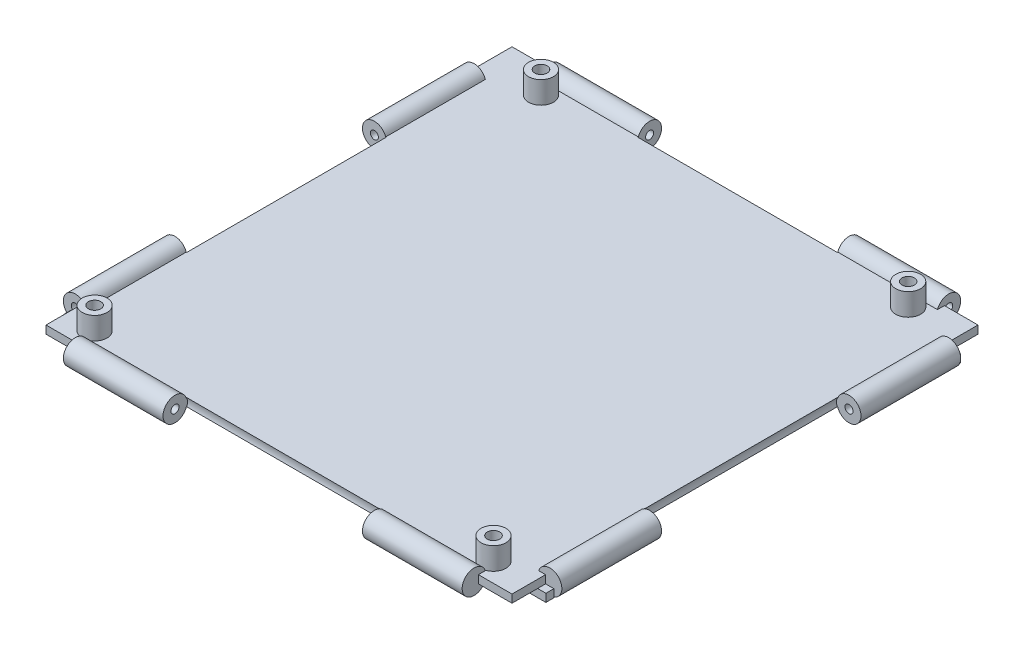
SolidWorks part; units mm, degrees
ref_plane "Front Plane" through (0, 0, 0) normal (0, 0, 1) x (1, 0, 0)
ref_plane "Top Plane" through (0, 0, 0) normal (0, 1, 0) x (1, 0, 0)
ref_plane "Right Plane" through (0, 0, 0) normal (1, 0, 0) x (0, 0, -1)
sketch "Sketch3" plane through (0, 0, 0) normal (0, 1, 0) x (1, 0, 0)
  line L1 (-48.5, -48.5) -> (48.5, -48.5)
  line L2 (-48.5, -48.5) -> (-48.5, 48.5)
  line L3 (-48.5, 48.5) -> (48.5, 48.5)
  line L4 (48.5, -48.5) -> (48.5, 48.5)
  line L5 (-48.5, -48.5) -> (48.5, 48.5) construction
  line L6 (-48.5, 48.5) -> (48.5, -48.5) construction
  point P0 (0, 0)
extrude "Boss-Extrude2" add sketch "Sketch3" along normal blind 1.6
sketch "Sketch6" plane through (0, 0, 48.5) normal (0, 0, 1) x (1, 0, 0)
  line L0 (-48.5, 1.6) -> (-48.5, 0) construction
  circle A0 centre (-47.6, 0.8) radius 2.4
  point P2 (-48.5, 0.8)
  point P5 (-48.5, 0.8)
  dimension "D1" = 0.9
  dimension "D2" = 0
extrude "Boss-Extrude3" add sketch "Sketch6" against normal blind 25
sketch "Sketch8" plane through (0, 0, 48.5) normal (0, 0, 1) x (1, 0, 0)
  line L0 (48.5, 1.6) -> (48.5, 0) construction
  line L1 (-45.3373, 0) -> (48.5, 0) construction
  circle A0 centre (47.6, 0.8) radius 2.4
  point P2 (48.5, 0.8)
  dimension "D1" = 0.9
  dimension "D2" = 0.8
extrude "Boss-Extrude4" add sketch "Sketch8" against normal blind 25
sketch "Sketch10" plane through (0, 0, -48.5) normal (0, 0, -1) x (-1, 0, 0)
  circle A0 centre (-47.6, 0.8) radius 2.4
extrude "Boss-Extrude5" add sketch "Sketch10" against normal blind 25
sketch "Sketch11" plane through (0, 0, -48.5) normal (0, 0, -1) x (-1, 0, 0)
  circle A0 centre (47.6, 0.8) radius 2.4
extrude "Boss-Extrude6" add sketch "Sketch11" against normal blind 25
sketch "Sketch12" plane through (-48.5, 0, 0) normal (-1, 0, 0) x (0, 0, 1)
  line L0 (-23.5, 3.2) -> (-48.5, 3.2) construction
  line L1 (-48.5, 3.2) -> (-48.5, -1.6) construction
  circle A0 centre (-47.6, 0.8) radius 2.4
  point P4 (-48.5, 0.8)
  dimension "D1" = 2.4
  dimension "D2" = 0.9
extrude "Boss-Extrude7" add sketch "Sketch12" against normal blind 25
sketch "Sketch13" plane through (-48.5, 0, 0) normal (-1, 0, 0) x (0, 0, 1)
  line L0 (48.5, 3.2) -> (23.5, 3.2) construction
  line L1 (48.5, -1.6) -> (48.5, 3.2) construction
  circle A0 centre (47.6, 0.8) radius 2.4
  dimension "D1" = 2.4
  dimension "D2" = 0.9
extrude "Boss-Extrude8" add sketch "Sketch13" against normal blind 25
sketch "Sketch15" plane through (48.5, 0, 0) normal (1, 0, 0) x (0, 0, -1)
  circle A0 centre (-47.6, 0.8) radius 2.4
extrude "Boss-Extrude9" add sketch "Sketch15" against normal blind 25
sketch "Sketch16" plane through (48.5, 0, 0) normal (1, 0, 0) x (0, 0, -1)
  circle A0 centre (47.6, 0.8) radius 2.4
extrude "Boss-Extrude10" add sketch "Sketch16" against normal blind 25
sketch "Sketch24" plane through (0, 0, 48.5) normal (0, 0, 1) x (1, 0, 0)
  line L1 (-45.2, -1.9741) -> (-50, -1.9741)
  line L2 (-45.2, -1.9741) -> (-45.2, 3.5741)
  line L3 (-45.2, 3.5741) -> (-50, 3.5741)
  line L4 (-50, -1.9741) -> (-50, 3.5741)
  line L5 (-45.2, -1.9741) -> (-50, 3.5741) construction
  line L6 (-45.2, 3.5741) -> (-50, -1.9741) construction
  point P0 (-47.6, 0.8)
extrude "Cut-Extrude6" cut sketch "Sketch24" against normal blind 3.3
sketch "Sketch25" plane through (0, 0, 48.5) normal (0, 0, -1) x (-1, 0, 0)
  line L1 (50, -1.6) -> (45.2, -1.6)
  line L2 (50, -1.6) -> (50, 3.2)
  line L3 (50, 3.2) -> (45.2, 3.2)
  line L4 (45.2, -1.6) -> (45.2, 3.2)
  line L5 (50, -1.6) -> (45.2, 3.2) construction
  line L6 (50, 3.2) -> (45.2, -1.6) construction
  point P0 (47.6, 0.8)
extrude "Cut-Extrude7" cut sketch "Sketch25" against normal blind 3.3
sketch "Sketch27" plane through (0, 0, -48.5) normal (0, 0, -1) x (-1, 0, 0)
  line L1 (45.2, -1.7788) -> (50, -1.7788)
  line L2 (45.2, -1.7788) -> (45.2, 3.3788)
  line L3 (45.2, 3.3788) -> (50, 3.3788)
  line L4 (50, -1.7788) -> (50, 3.3788)
  line L5 (45.2, -1.7788) -> (50, 3.3788) construction
  line L6 (45.2, 3.3788) -> (50, -1.7788) construction
  point P0 (47.6, 0.8)
extrude "Cut-Extrude8" cut sketch "Sketch27" against normal blind 3.3
sketch "Sketch28" plane through (0, 0, -45.2) normal (0, 0, -1) x (-1, 0, 0)
  line L1 (50, -1.6) -> (45.2, -1.6)
  line L2 (50, -1.6) -> (50, 3.2)
  line L3 (50, 3.2) -> (45.2, 3.2)
  line L4 (45.2, -1.6) -> (45.2, 3.2)
  line L5 (50, -1.6) -> (45.2, 3.2) construction
  line L6 (50, 3.2) -> (45.2, -1.6) construction
  point P0 (47.6, 0.8)
extrude "Cut-Extrude9" cut sketch "Sketch28" along normal blind 6
sketch "Sketch29" plane through (0, 0, 48.5) normal (0, 0, 1) x (1, 0, 0)
  line L1 (45.2, -1.9133) -> (50, -1.9133)
  line L2 (45.2, -1.9133) -> (45.2, 3.5133)
  line L3 (45.2, 3.5133) -> (50, 3.5133)
  line L4 (50, -1.9133) -> (50, 3.5133)
  line L5 (45.2, -1.9133) -> (50, 3.5133) construction
  line L6 (45.2, 3.5133) -> (50, -1.9133) construction
  point P0 (47.6, 0.8)
extrude "Cut-Extrude10" cut sketch "Sketch29" against normal blind 3.3
sketch "Sketch30" plane through (0, 0, 48.5) normal (0, 0, -1) x (-1, 0, 0)
  line L1 (-45.2, 3.2) -> (-50.2988, 3.2)
  line L2 (-45.2, 3.2) -> (-45.2, -1.6)
  line L3 (-45.2, -1.6) -> (-50.2988, -1.6)
  line L4 (-50.2988, 3.2) -> (-50.2988, -1.6)
extrude "Cut-Extrude11" cut sketch "Sketch30" against normal blind 3.3
sketch "Sketch31" plane through (0, 0, -48.5) normal (0, 0, -1) x (-1, 0, 0)
  line L1 (-45.2, -1.9404) -> (-50, -1.9404)
  line L2 (-45.2, -1.9404) -> (-45.2, 3.5404)
  line L3 (-45.2, 3.5404) -> (-50, 3.5404)
  line L4 (-50, -1.9404) -> (-50, 3.5404)
  line L5 (-45.2, -1.9404) -> (-50, 3.5404) construction
  line L6 (-45.2, 3.5404) -> (-50, -1.9404) construction
  point P0 (-47.6, 0.8)
extrude "Cut-Extrude12" cut sketch "Sketch31" against normal blind 3.3
sketch "Sketch32" plane through (0, 0, -48.5) normal (0, 0, 1) x (1, 0, 0)
  line L1 (45.2, 3.2) -> (50.1875, 3.2)
  line L2 (45.2, 3.2) -> (45.2, -1.6)
  line L3 (45.2, -1.6) -> (50.1875, -1.6)
  line L4 (50.1875, 3.2) -> (50.1875, -1.6)
extrude "Cut-Extrude13" cut sketch "Sketch32" against normal blind 3.3
sketch "Sketch38" plane through (0, 0, -23.5) normal (0, 0, 1) x (1, 0, 0)
  circle A0 centre (-47.6, 0.8) radius 2.4
extrude "Boss-Extrude11" add sketch "Sketch38" along normal blind 1
sketch "Sketch39" plane through (0, 0, 23.5) normal (0, 0, -1) x (-1, 0, 0)
  circle A0 centre (47.6, 0.8) radius 2.4
extrude "Boss-Extrude12" add sketch "Sketch39" along normal blind 1
sketch "Sketch42" plane through (0, 0, -23.5) normal (0, 0, 1) x (1, 0, 0)
  circle A0 centre (47.6, 0.8) radius 2.4
extrude "Boss-Extrude13" add sketch "Sketch42" along normal blind 1
sketch "Sketch43" plane through (0, 0, 23.5) normal (0, 0, -1) x (-1, 0, 0)
  circle A0 centre (-47.6, 0.8) radius 2.4
extrude "Boss-Extrude14" add sketch "Sketch43" along normal blind 1
sketch "Sketch44" plane through (23.5, 0, 0) normal (-1, 0, 0) x (0, 0, 1)
  circle A0 centre (-47.6, 0.8) radius 2.4
extrude "Boss-Extrude15" add sketch "Sketch44" along normal blind 1
sketch "Sketch45" plane through (-23.5, 0, 0) normal (1, 0, 0) x (0, 0, -1)
  circle A0 centre (47.6, 0.8) radius 2.4
extrude "Boss-Extrude16" add sketch "Sketch45" along normal blind 1
sketch "Sketch46" plane through (23.5, 0, 0) normal (-1, 0, 0) x (0, 0, 1)
  circle A0 centre (47.6, 0.8) radius 2.4
extrude "Boss-Extrude17" add sketch "Sketch46" along normal blind 1
sketch "Sketch47" plane through (-23.5, 0, 0) normal (1, 0, 0) x (0, 0, -1)
  circle A0 centre (-47.6, 0.8) radius 2.4
extrude "Boss-Extrude18" add sketch "Sketch47" along normal blind 1
sketch "Sketch69" plane through (0, 0, 45.2) normal (0, 0, 1) x (1, 0, 0)
  line L0 (-45.3373, 1.6) -> (-46.7373, 1.6)
  line L1 (-46.7373, 1.6) -> (-46.7373, 0)
  line L2 (-46.7373, 0) -> (-45.3373, 0)
  line L3 (-45.3373, 0) -> (-45.3373, -2.2963)
  line L4 (-45.3373, -2.2963) -> (-50.8618, -2.2963)
  line L5 (-50.8618, -2.2963) -> (-50.8618, 4.0891)
  line L6 (-50.8618, 4.0891) -> (-45.3373, 4.0891)
  line L7 (-45.3373, 4.0891) -> (-45.3373, 1.6)
extrude "Cut-Extrude24" cut sketch "Sketch69" against normal blind 5.2
sketch "Sketch72" plane through (0, 0, 45.2) normal (0, 0, 1) x (1, 0, 0)
  line L0 (45.3373, 1.6) -> (46.7373, 1.6)
  line L1 (46.7373, 1.6) -> (46.7373, 0)
  line L2 (46.7373, 0) -> (45.3373, 0)
  line L3 (45.3373, 0) -> (45.3373, -2.332)
  line L4 (45.3373, -2.332) -> (51.5664, -2.332)
  line L5 (51.5664, -2.332) -> (51.5664, 3.8868)
  line L6 (51.5664, 3.8868) -> (45.3373, 3.8868)
  line L7 (45.3373, 3.8868) -> (45.3373, 1.6)
extrude "Cut-Extrude25" cut sketch "Sketch72" against normal blind 5.2
sketch "Sketch74" plane through (0, 0, -45.2) normal (0, 0, -1) x (-1, 0, 0)
  line L0 (-45.3373, 1.6) -> (-46.7373, 1.6)
  line L1 (-46.7373, 1.6) -> (-46.7373, 0)
  line L2 (-46.7373, 0) -> (-45.3373, 0)
  line L3 (-45.3373, 0) -> (-45.3373, -2.1525)
  line L4 (-45.3373, -2.1525) -> (-50.4022, -2.1525)
  line L5 (-50.4022, -2.1525) -> (-50.4022, 3.9519)
  line L6 (-50.4022, 3.9519) -> (-45.3373, 3.9519)
  line L7 (-45.3373, 3.9519) -> (-45.3373, 1.6)
extrude "Cut-Extrude26" cut sketch "Sketch74" against normal blind 5.2
sketch "Sketch75" plane through (0, 0, -45.2) normal (0, 0, -1) x (-1, 0, 0)
  line L0 (45.3373, 1.6) -> (46.7373, 1.6)
  line L1 (46.7373, 1.6) -> (46.7373, 0)
  line L2 (46.7373, 0) -> (45.3373, 0)
  line L3 (45.3373, 0) -> (45.3373, -1.8864)
  line L4 (45.3373, -1.8864) -> (51.292, -1.8864)
  line L5 (51.292, -1.8864) -> (51.292, 3.8238)
  line L6 (51.292, 3.8238) -> (45.3373, 3.8238)
  line L7 (45.3373, 3.8238) -> (45.3373, 1.6)
extrude "Cut-Extrude27" cut sketch "Sketch75" against normal blind 5.2
sketch "Sketch77" plane through (-45.2, 0, 0) normal (-1, 0, 0) x (0, 0, 1)
  line L0 (-45.3373, 1.6) -> (-45.3373, 4.0728)
  line L1 (-45.3373, 4.0728) -> (-50.7539, 4.0728)
  line L2 (-50.7539, 4.0728) -> (-50.7539, -2.0737)
  line L3 (-50.7539, -2.0737) -> (-45.3373, -2.0737)
  line L4 (-45.3373, -2.0737) -> (-45.3373, 0)
  line L5 (-45.3373, 0) -> (-46.7373, 0)
  line L6 (-46.7373, 0) -> (-46.7373, 1.6)
  line L7 (-46.7373, 1.6) -> (-45.3373, 1.6)
extrude "Cut-Extrude29" cut sketch "Sketch77" against normal blind 5.2
sketch "Sketch78" plane through (-45.2, 0, 0) normal (-1, 0, 0) x (0, 0, 1)
  line L0 (45.3373, 1.6) -> (45.3373, 3.5518)
  line L1 (45.3373, 3.5518) -> (50.6981, 3.5518)
  line L2 (50.6981, 3.5518) -> (50.6981, -1.7977)
  line L3 (50.6981, -1.7977) -> (45.3373, -1.7977)
  line L4 (45.3373, -1.7977) -> (45.3373, 0)
  line L5 (45.3373, 0) -> (46.7373, 0)
  line L6 (46.7373, 0) -> (46.7373, 1.6)
  line L7 (46.7373, 1.6) -> (45.3373, 1.6)
extrude "Cut-Extrude30" cut sketch "Sketch78" against normal blind 5.2
sketch "Sketch79" plane through (45.2, 0, 0) normal (1, 0, 0) x (0, 0, -1)
  line L0 (-45.3373, 1.6) -> (-45.3373, 4.0003)
  line L1 (-45.3373, 4.0003) -> (-50.7843, 4.0003)
  line L2 (-50.7843, 4.0003) -> (-50.7843, -1.8519)
  line L3 (-50.7843, -1.8519) -> (-45.3373, -1.8519)
  line L4 (-45.3373, -1.8519) -> (-45.3373, 0)
  line L5 (-45.3373, 0) -> (-46.7373, 0)
  line L6 (-46.7373, 0) -> (-46.7373, 1.6)
  line L7 (-46.7373, 1.6) -> (-45.3373, 1.6)
extrude "Cut-Extrude31" cut sketch "Sketch79" against normal blind 5.2
sketch "Sketch80" plane through (45.2, 0, 0) normal (1, 0, 0) x (0, 0, -1)
  line L0 (45.3373, 1.6) -> (45.3373, 3.7938)
  line L1 (45.3373, 3.7938) -> (50.5196, 3.7938)
  line L2 (50.5196, 3.7938) -> (50.5196, -2.0451)
  line L3 (50.5196, -2.0451) -> (45.3373, -2.0451)
  line L4 (45.3373, -2.0451) -> (45.3373, 0)
  line L5 (45.3373, 0) -> (46.7373, 0)
  line L6 (46.7373, 0) -> (46.7373, 1.6)
  line L7 (46.7373, 1.6) -> (45.3373, 1.6)
extrude "Cut-Extrude32" cut sketch "Sketch80" against normal blind 5.2
sketch "Sketch81" plane through (0, 1.6, 0) normal (0, 1, 0) x (1, 0, 0)
  line L1 (-45.2, 46.7373) -> (-46.7373, 46.7373)
  line L2 (-45.2, 46.7373) -> (-45.2, 45.2)
  line L3 (-45.2, 45.2) -> (-46.7373, 45.2)
  line L4 (-46.7373, 46.7373) -> (-46.7373, 45.2)
extrude "Boss-Extrude21" add sketch "Sketch81" against normal blind 1.6
sketch "Sketch82" plane through (0, 1.6, 0) normal (0, 1, 0) x (1, 0, 0)
  line L1 (45.2, 46.7373) -> (46.7373, 46.7373)
  line L2 (45.2, 46.7373) -> (45.2, 45.2)
  line L3 (45.2, 45.2) -> (46.7373, 45.2)
  line L4 (46.7373, 46.7373) -> (46.7373, 45.2)
extrude "Boss-Extrude22" add sketch "Sketch82" against normal blind 1.6
sketch "Sketch83" plane through (0, 1.6, 0) normal (0, 1, 0) x (1, 0, 0)
  line L1 (-46.7373, -45.2) -> (-45.2, -45.2)
  line L2 (-46.7373, -45.2) -> (-46.7373, -46.7373)
  line L3 (-46.7373, -46.7373) -> (-45.2, -46.7373)
  line L4 (-45.2, -45.2) -> (-45.2, -46.7373)
extrude "Boss-Extrude23" add sketch "Sketch83" against normal blind 1.6
sketch "Sketch84" plane through (0, 1.6, 0) normal (0, 1, 0) x (1, 0, 0)
  line L1 (46.7373, -45.2) -> (45.2, -45.2)
  line L2 (46.7373, -45.2) -> (46.7373, -46.7373)
  line L3 (46.7373, -46.7373) -> (45.2, -46.7373)
  line L4 (45.2, -45.2) -> (45.2, -46.7373)
extrude "Boss-Extrude24" add sketch "Sketch84" against normal blind 1.6
sketch "Sketch87" plane through (-22.5, 0, 0) normal (1, 0, 0) x (0, 0, -1)
  circle A0 centre (-47.6, 0.8) radius 2.4
extrude "Boss-Extrude25" add sketch "Sketch87" along normal blind 2.5
sketch "Sketch88" plane through (22.5, 0, 0) normal (-1, 0, 0) x (0, 0, 1)
  circle A0 centre (47.6, 0.8) radius 2.4
extrude "Boss-Extrude26" add sketch "Sketch88" along normal blind 2.5
sketch "Sketch91" plane through (-20, 0, 0) normal (1, 0, 0) x (0, 0, -1)
  circle A0 centre (-47.6, 0.8) radius 2.5
extrude "Cut-Extrude33" cut sketch "Sketch91" along normal blind 40
sketch "Sketch93" plane through (0, 0, -22.5) normal (0, 0, 1) x (1, 0, 0)
  circle A0 centre (-47.6, 0.8) radius 2.4
extrude "Boss-Extrude27" add sketch "Sketch93" along normal blind 2.5
sketch "Sketch94" plane through (0, 0, 22.5) normal (0, 0, -1) x (-1, 0, 0)
  circle A0 centre (47.6, 0.8) radius 2.4
extrude "Boss-Extrude28" add sketch "Sketch94" along normal blind 2.5
sketch "Sketch97" plane through (0, 0, -20) normal (0, 0, 1) x (1, 0, 0)
  circle A0 centre (-47.6, 0.8) radius 2.5
extrude "Cut-Extrude34" cut sketch "Sketch97" along normal blind 40
sketch "Sketch98" plane through (0, 0, -22.5) normal (0, 0, 1) x (1, 0, 0)
  circle A0 centre (47.6, 0.8) radius 2.4
extrude "Boss-Extrude29" add sketch "Sketch98" along normal blind 2.5
sketch "Sketch99" plane through (0, 0, 22.5) normal (0, 0, -1) x (-1, 0, 0)
  circle A0 centre (-47.6, 0.8) radius 2.4
extrude "Boss-Extrude30" add sketch "Sketch99" along normal blind 2.5
sketch "Sketch100" plane through (0, 0, -20) normal (0, 0, 1) x (1, 0, 0)
  circle A0 centre (47.6, 0.8) radius 2.5
extrude "Cut-Extrude35" cut sketch "Sketch100" along normal blind 40
sketch "Sketch101" plane through (-22.5, 0, 0) normal (1, 0, 0) x (0, 0, -1)
  circle A0 centre (47.6, 0.8) radius 2.4
extrude "Boss-Extrude31" add sketch "Sketch101" along normal blind 2.5
sketch "Sketch102" plane through (22.5, 0, 0) normal (-1, 0, 0) x (0, 0, 1)
  circle A0 centre (-47.6, 0.8) radius 2.4
extrude "Boss-Extrude32" add sketch "Sketch102" along normal blind 2.5
sketch "Sketch104" plane through (-20, 0, 0) normal (1, 0, 0) x (0, 0, -1)
  circle A0 centre (47.6, 0.8) radius 2.5
extrude "Cut-Extrude36" cut sketch "Sketch104" along normal blind 40
sketch "Sketch105" plane through (0, 0, 40) normal (0, 0, 1) x (1, 0, 0)
  circle A0 centre (-47.6, 0.8) radius 0.81
extrude "Cut-Extrude37" cut sketch "Sketch105" against normal blind 78.5
sketch "Sketch106" plane through (-40, 0, 0) normal (-1, 0, 0) x (0, 0, 1)
  circle A0 centre (47.6, 0.8) radius 0.81
extrude "Cut-Extrude38" cut sketch "Sketch106" against normal blind 78.5
sketch "Sketch107" plane through (40, 0, 0) normal (1, 0, 0) x (0, 0, -1)
  circle A0 centre (47.6, 0.8) radius 0.81
extrude "Cut-Extrude39" cut sketch "Sketch107" against normal blind 78.5
sketch "Sketch108" plane through (0, 0, -40) normal (0, 0, -1) x (-1, 0, 0)
  circle A0 centre (-47.6, 0.8) radius 0.81
extrude "Cut-Extrude40" cut sketch "Sketch108" against normal blind 78.5
sketch "Sketch135" plane through (0, 1.6, 0) normal (0, 1, 0) x (1, 0, 0)
  line L2 (28.1604, 35.2315) -> (0, 7.0711)
  line L3 (0, 7.0711) -> (-28.1604, 35.2315)
  line L4 (-28.1604, 35.2315) -> (28.1604, 35.2315)
  line L5 (-20, 45.2315) -> (20, 45.2315) construction
  dimension "D1" = 10
extrude "Cut-Extrude47" cut sketch "Sketch135" against normal blind 20
sketch "Sketch136" plane through (0, 1.6, 0) normal (0, 1, 0) x (1, 0, 0)
  line L2 (-28.1604, -35.2315) -> (0, -7.0711)
  line L3 (0, -7.0711) -> (28.1604, -35.2315)
  line L4 (28.1604, -35.2315) -> (-28.1604, -35.2315)
  line L5 (20, -45.2315) -> (-20, -45.2315) construction
  dimension "D3" = 10
extrude "Cut-Extrude48" cut sketch "Sketch136" against normal blind 20
sketch "Sketch137" plane through (0, 1.6, 0) normal (0, 1, 0) x (1, 0, 0)
  line L0 (35.2315, 28.1604) -> (7.0711, 0)
  line L1 (7.0711, 0) -> (35.2315, -28.1604)
  line L2 (35.2315, -28.1604) -> (35.2315, 28.1604)
  line L3 (0, 7.0711) -> (28.1604, 35.2315) construction
  line L4 (28.1604, -35.2315) -> (0, -7.0711) construction
  line L5 (45.2315, 20) -> (45.2315, -20) construction
  dimension "D1" = 10
  dimension "D2" = 10
  dimension "D3" = 10
extrude "Cut-Extrude49" cut sketch "Sketch137" against normal blind 20
sketch "Sketch138" plane through (0, 1.6, 0) normal (0, 1, 0) x (1, 0, 0)
  line L0 (-35.2315, 28.1604) -> (-7.0711, 0)
  line L1 (-7.0711, 0) -> (-35.2315, -28.1604)
  line L2 (-35.2315, -28.1604) -> (-35.2315, 28.1604)
  line L3 (-45.2315, -20) -> (-45.2315, 20) construction
  line L4 (0, -7.0711) -> (-28.1604, -35.2315) construction
  line L5 (-28.1604, 35.2315) -> (0, 7.0711) construction
  dimension "D1" = 10
  dimension "D2" = 10
  dimension "D3" = 10
extrude "Cut-Extrude50" cut sketch "Sketch138" against normal blind 20
sketch "Sketch139" plane through (0, 1.6, 0) normal (0, 1, 0) x (1, 0, 0)
  circle A0 centre (0, 0) radius 15
extrude "Boss-Extrude40" add sketch "Sketch139" against normal blind 1.6
sketch "Sketch140" plane through (0, 1.6, 0) normal (0, 1, 0) x (1, 0, 0)
  circle A0 centre (0, 0) radius 5
extrude "Cut-Extrude51" cut sketch "Sketch140" against normal blind 1.6
fillet "Fillet7" radius 2 16 edges at (28.1604, 0.8, -35.2315) (35.2315, 0.8, -28.1604) (35.2315, 0.8, 28.1604) (28.1604, 0.8, 35.2315) (-28.1604, 0.8, 35.2315) (-13.5355, 0.8, -6.4645) (-13.5355, 0.8, 6.4645) (-35.2315, 0.8, 28.1604) (6.4645, 0.8, -13.5355) (-6.4645, 0.8, -13.5355) (13.5355, 0.8, 6.4645) (13.5355, 0.8, -6.4645) (-6.4645, 0.8, 13.5355) (6.4645, 0.8, 13.5355) (-35.2315, 0.8, -28.1604) (-28.1604, 0.8, -35.2315)
sketch "Sketch119" plane through (0, 1.6, 0) normal (0, 1, 0) x (1, 0, 0)
  line L2 (-28.1604, 35.2315) -> (28.1604, 35.2315)
  line L3 (28.1604, 35.2315) -> (0, 7.0711)
  line L4 (0, 7.0711) -> (-28.1604, 35.2315)
  line L5 (-20, 45.2315) -> (20, 45.2315) construction
  dimension "D1" = 10
extrude "Cut-Extrude41" cut sketch "Sketch119" against normal blind 1.6
sketch "Sketch120" plane through (0, 1.6, 0) normal (0, 1, 0) x (1, 0, 0)
  line L2 (-28.1604, -35.2315) -> (28.1604, -35.2315)
  line L3 (28.1604, -35.2315) -> (0, -7.0711)
  line L4 (-28.1604, -35.2315) -> (0, -7.0711)
  line L5 (20, -45.2315) -> (-20, -45.2315) construction
  dimension "D3" = 10
extrude "Cut-Extrude42" cut sketch "Sketch120" against normal blind 1.6
sketch "Sketch121" plane through (0, 1.6, 0) normal (0, 1, 0) x (1, 0, 0)
  line L0 (-35.2315, 28.1604) -> (-35.2315, -28.1604)
  line L1 (-35.2315, -28.1604) -> (-7.0711, 0)
  line L2 (-35.2315, 28.1604) -> (-7.0711, 0)
  line L3 (-28.1604, 35.2315) -> (0, 7.0711) construction
  line L4 (0, -7.0711) -> (-28.1604, -35.2315) construction
  line L5 (-45.2315, -20) -> (-45.2315, 20) construction
  dimension "D1" = 10
  dimension "D2" = 10
  dimension "D3" = 10
extrude "Cut-Extrude43" cut sketch "Sketch121" against normal blind 1.6
sketch "Sketch122" plane through (0, 1.6, 0) normal (0, 1, 0) x (1, 0, 0)
  line L0 (35.2315, 28.1604) -> (35.2315, -28.1604)
  line L1 (35.2315, -28.1604) -> (7.0711, 0)
  line L2 (35.2315, 28.1604) -> (7.0711, 0)
  line L3 (0, 7.0711) -> (28.1604, 35.2315) construction
  line L4 (28.1604, -35.2315) -> (0, -7.0711) construction
  line L5 (45.2315, 20) -> (45.2315, -20) construction
  dimension "D1" = 10
  dimension "D2" = 10
  dimension "D3" = 10
extrude "Cut-Extrude44" cut sketch "Sketch122" against normal blind 1.6
sketch "Sketch123" plane through (0, 1.6, 0) normal (0, 1, 0) x (1, 0, 0)
  circle A0 centre (0, 0) radius 15
extrude "Boss-Extrude35" add sketch "Sketch123" against normal blind 1.6
sketch "Sketch124" plane through (0, 1.6, 0) normal (0, 1, 0) x (1, 0, 0)
  circle A0 centre (0, 0) radius 5
extrude "Cut-Extrude45" cut sketch "Sketch124" against normal blind 1.6
fillet "Fillet4" radius 2 16 edges at (35.2315, 0.8, 28.1604) (35.2315, 0.8, -28.1604) (-6.4645, 0.8, 13.5355) (6.4645, 0.8, 13.5355) (28.1604, 0.8, 35.2315) (13.5355, 0.8, -6.4645) (13.5355, 0.8, 6.4645) (-28.1604, 0.8, 35.2315) (-13.5355, 0.8, 6.4645) (-13.5355, 0.8, -6.4645) (28.1604, 0.8, -35.2315) (-28.1604, 0.8, -35.2315) (6.4645, 0.8, -13.5355) (-6.4645, 0.8, -13.5355) (-35.2315, 0.8, 28.1604) (-35.2315, 0.8, -28.1604)
sketch "Sketch144" plane through (0, 0, -46.7373) normal (0, 0, -1) x (-1, 0, 0)
  line L1 (46.7373, 1.6) -> (40, 1.6)
  line L2 (46.7373, 1.6) -> (46.7373, 0)
  line L3 (46.7373, 0) -> (40, 0)
  line L4 (40, 1.6) -> (40, 0)
extrude "Boss-Extrude42" add sketch "Sketch144" along normal blind 1.6
sketch "Sketch145" plane through (-46.7373, 0, 0) normal (-1, 0, 0) x (0, 0, 1)
  line L1 (-48.3373, 1.6) -> (-40, 1.6)
  line L2 (-48.3373, 1.6) -> (-48.3373, 0)
  line L3 (-48.3373, 0) -> (-40, 0)
  line L4 (-40, 1.6) -> (-40, 0)
extrude "Boss-Extrude43" add sketch "Sketch145" along normal blind 1.6
sketch "Sketch147" plane through (0, 0, 0) normal (0, -1, 0) x (1, 0, 0)
  line L0 (-40, -40) -> (-48.4, -40)
  line L1 (-50, -40) -> (-45.3373, -40) construction
  line L2 (-48.4, -40) -> (-48.4, -41.6)
  line L3 (-48.4, -41.6) -> (-40, -41.6)
  line L4 (-40, -41.6) -> (-40, -40)
  line L5 (-40, -45.3373) -> (-40, -48.3373) construction
  dimension "D1" = 1.6
  dimension "D2" = 8.4
  dimension "D3" = 0
extrude "Boss-Extrude44" add sketch "Sketch147" along normal blind 1.6
sketch "Sketch149" plane through (0, 0, 0) normal (0, -1, 0) x (1, 0, 0)
  line L0 (-45.3373, 40) -> (-50, 40) construction
  line L1 (-48.4, 40) -> (-40, 40)
  line L3 (-48.4, 40) -> (-48.4, 41.6)
  line L4 (-48.4, 41.6) -> (-40, 41.6)
  line L6 (-40, 40) -> (-40, 41.6)
  line L7 (-40, 50) -> (-40, 45.3373) construction
  dimension "D1" = 1.6
  dimension "D2" = 0
  dimension "D3" = 8.4
extrude "Boss-Extrude45" add sketch "Sketch149" along normal blind 1.6
sketch "Sketch150" plane through (0, 0, 0) normal (0, -1, 0) x (1, 0, 0)
  line L0 (45.3373, -40) -> (50, -40) construction
  line L1 (48.4, -40) -> (40, -40)
  line L2 (48.4, -40) -> (48.4, -41.6)
  line L3 (48.4, -41.6) -> (40, -41.6)
  line L4 (40, -40) -> (40, -41.6)
  dimension "D1" = 1.6
  dimension "D2" = 8.4
extrude "Boss-Extrude46" add sketch "Sketch150" along normal blind 1.6
sketch "Sketch151" plane through (0, 0, 0) normal (0, -1, 0) x (1, 0, 0)
  line L0 (40, 45.3373) -> (40, 50) construction
  line L1 (40, 41.6) -> (48.4, 41.6)
  line L2 (40, 41.6) -> (40, 40)
  line L3 (40, 40) -> (48.4, 40)
  line L4 (48.4, 41.6) -> (48.4, 40)
  line L5 (50, 40) -> (45.3373, 40) construction
  dimension "D1" = 1.6
  dimension "D2" = 8.4
extrude "Boss-Extrude47" add sketch "Sketch151" along normal blind 1.6
fillet "Fillet12" radius 1 4 edges at (40, -0.8, 40) (40, -0.8, -40) (-40, -0.8, -40) (-40, -0.8, 40)
sketch "Sketch176" plane through (0, 0, 0) normal (0, -1, 0) x (1, 0, 0)
  line L1 (-42.4946, -44.8554) -> (42.4946, -44.8554)
  line L2 (-42.4946, -44.8554) -> (-42.4946, 44.8554)
  line L3 (-42.4946, 44.8554) -> (42.4946, 44.8554)
  line L4 (42.4946, -44.8554) -> (42.4946, 44.8554)
  line L5 (-42.4946, -44.8554) -> (42.4946, 44.8554) construction
  line L6 (-42.4946, 44.8554) -> (42.4946, -44.8554) construction
  point P0 (0, 0)
extrude "Boss-Extrude58" add sketch "Sketch176" against normal blind 1.6
sketch "Sketch177" plane through (0, 1.6, 0) normal (0, 1, 0) x (1, 0, 0)
  circle A0 centre (-40.8433, -42.8781) radius 2.5
  circle A1 centre (39.1667, -42.8781) radius 2.5
  circle A2 centre (-37.0333, 42.8469) radius 2.5
  circle A3 centre (36.6267, 42.8469) radius 2.5
  dimension "D1" = 5
  dimension "D2" = 80.01
  dimension "D3" = 85.725
  dimension "D4" = 3.81
  dimension "D5" = 73.66
extrude "Boss-Extrude59" add sketch "Sketch177" along normal blind 4.45
hole_wizard "M3x0.5 Tapped Hole1" positions "Sketch179" profile "Sketch178" tap size "M3x0.5" standard "ANSI Metric"
sketch "Sketch179" plane through (0, 6.05, 0) normal (0, 1, 0) x (1, 0, 0)
  point P0 (-40.8433, -42.8781)
  point P3 (39.1667, -42.8781)
  point P6 (36.6267, 42.8469)
  point P9 (-37.0333, 42.8469)
sketch "Sketch178" plane through (-40.8433, 6.05, 42.8781) normal (1, 0, 0) x (0, 0, 1)
  line L0 (0, 0) -> (0, 5.2011)
  line L1 (0, 5.2011) -> (1.25, 4.45)
  line L2 (1.25, 4.45) -> (1.25, 0)
  line L5 (1.25, 0) -> (0, 0)
  line L10 (0, 5.2011) -> (-1.25, 4.45) construction
  line L11 (0, -6.35) -> (0, 107.95) construction
  dimension "Tap Drill Dia." = 2.5
  dimension "Tap Drill Depth" = 4.45
  dimension "Drill Angle" = 118
cosmetic thread "Hole Thread1" parameters "D1"=4.45, "D2"=3
cosmetic thread "Hole Thread2" parameters "D1"=4.45, "D2"=3
cosmetic thread "Hole Thread3" parameters "D1"=4.45, "D2"=3
cosmetic thread "Hole Thread4" parameters "D1"=4.45, "D2"=3
